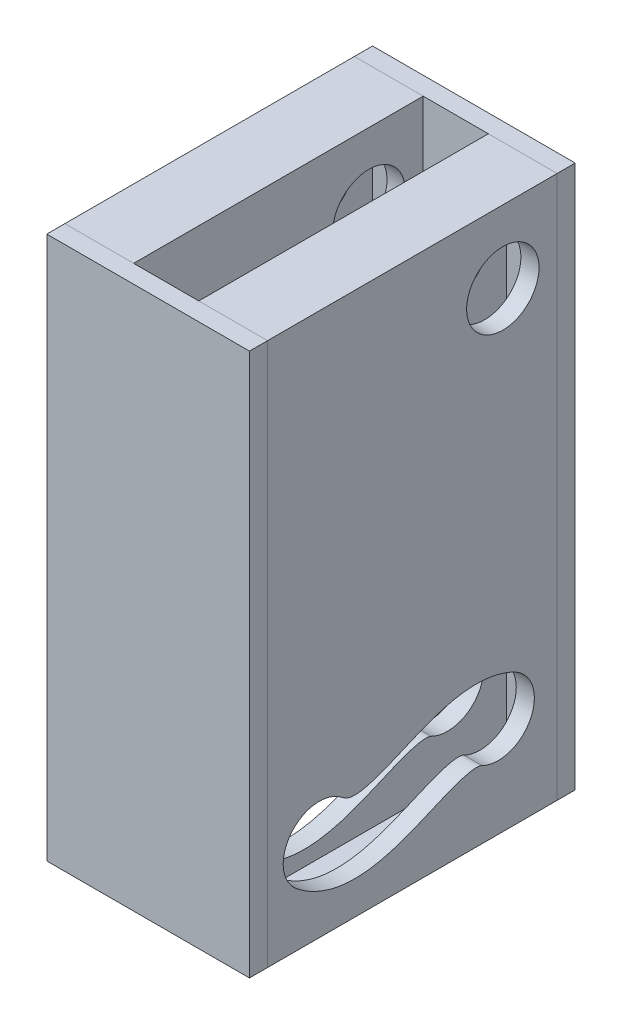
SolidWorks part; units mm, degrees
ref_plane "Front Plane" through (0, 0, 0) normal (0, 0, 1) x (1, 0, 0)
ref_plane "Top Plane" through (0, 0, 0) normal (0, 1, 0) x (1, 0, 0)
ref_plane "Right Plane" through (0, 0, 0) normal (1, 0, 0) x (0, 0, -1)
sketch "Sketch1" plane through (0, 0, 0) normal (0, 0, 1) x (1, 0, 0)
  line L0 (-9, 75) -> (-9, 35)
  line L8 (-9, -35) -> (-9, -75)
  line L9 (-9, -75) -> (-28, -75)
  line L10 (-28, -75) -> (-28, 75)
  line L11 (-28, 75) -> (-9, 75)
  line L12 (0, 171.0434) -> (0, -171.0434) construction
  line L13 (-9, 35) -> (9, 35)
  line L14 (-9, -35) -> (9, -35)
  line L15 (9, -35) -> (9, -75)
  line L16 (9, -75) -> (28, -75)
  line L17 (28, -75) -> (28, 75)
  line L18 (9, 75) -> (9, 35)
  line L19 (28, 75) -> (9, 75)
  line L20 (-23, 70) -> (-14, 70)
  line L21 (-14, 70) -> (-14, 30)
  line L22 (-14, 30) -> (14, 30)
  line L23 (14, 70) -> (14, 30)
  line L24 (23, 70) -> (14, 70)
  line L25 (23, -70) -> (23, 70)
  line L26 (14, -70) -> (23, -70)
  line L27 (14, -30) -> (14, -70)
  line L28 (-14, -30) -> (14, -30)
  line L29 (-14, -30) -> (-14, -70)
  line L30 (-14, -70) -> (-23, -70)
  line L31 (-23, -70) -> (-23, 70)
  line L32 (-66.2515, 55) -> (66.2515, 55) construction
  line L33 (-23, 0) -> (23, 0) construction
  line L34 (-28, 65) -> (28, 65) construction
  line L35 (-28, -65) -> (28, -65) construction
  line L36 (-66.2515, -55) -> (66.2515, -55) construction
  point P6 (0, -35)
  point P16 (0, 35)
  point P31 (0, 0)
  point P34 (0, 55)
  point P35 (-9, 55)
  dimension "D2" = 10
  dimension "D3" = 18
  dimension "D4" = 56
  dimension "D5" = 150
  dimension "D6" = 20
  dimension "D1" = 5
sketch "Sketch2" plane through (0, 0, 0) normal (1, 0, 0) x (0, 0, -1)
  line L0 (-30, 0) -> (50, 0) construction
  line L1 (-30, 0) -> (-35, 0) construction
  line L2 (50, 0) -> (55, 0) construction
  dimension "D1" = 80
  dimension "D2" = 5
  dimension "D3" = 50
extrude "Boss-Extrude1" add sketch "Sketch1" along normal up to vertex (30 mm away) and the other way up to vertex (50 mm away) up to point (0, 0, 30) other way up to point (0, 0, -50)
sketch "Sketch3" plane through (0, 0, 0) normal (0, 0, 1) x (1, 0, 0)
  line L1 (-28, -75) -> (28, -75)
  line L2 (-28, -75) -> (-28, 75)
  line L3 (-28, 75) -> (28, 75)
  line L4 (28, -75) -> (28, 75)
  line L5 (-28, -75) -> (28, 75) construction
  line L6 (-28, 75) -> (28, -75) construction
  point P0 (0, 0)
extrude "Boss-Extrude2" add sketch "Sketch3" along normal up to vertex (35 mm away) from vertex separate body up to point (0, 0, 35) starting at point (0, 0, 30)
extrude "Boss-Extrude3" add sketch "Sketch3<2>" against normal up to vertex (55 mm away) from vertex separate body up to point (0, 0, -55) starting at point (0, 0, -50)
sketch "Sketch3<2>" plane through (0, 0, 0) normal (0, 0, 1) x (1, 0, 0) same geometry as "Sketch3"
sketch "Sketch4" plane through (0, 0, 0) normal (1, 0, 0) x (0, 0, -1)
  line L0 (0, 171.0434) -> (0, -171.0434) construction
  line L1 (0, 0) -> (0, 55) construction
  line L2 (0, 55) -> (35, 55) construction
  line L3 (-11.8844, -55.7997) -> (0.1156, -55.7997) construction
  line L5 (-10.8844, -60.7997) -> (-0.8844, -60.7997) construction
  line L6 (-10.8844, -60.7997) -> (-10.8844, -50.7997) construction
  line L7 (-10.8844, -50.7997) -> (-0.8844, -50.7997) construction
  line L8 (-0.8844, -60.7997) -> (-0.8844, -50.7997) construction
  line L9 (-10.8844, -60.7997) -> (-0.8844, -50.7997) construction
  line L10 (-10.8844, -50.7997) -> (-0.8844, -60.7997) construction
  arc A2 (-21.9612, -60.1535) -> (-9.4142, -44.5787) centre (-15.6877, -52.3661) cw
  arc A3 (29.2096, -56.2677) -> (38.2188, -38.4118) centre (33.7142, -47.3397) ccw
  circle A4 centre (35, 55) radius 10
  spline S0 degree 3 poles (-15.6877, -52.3661) (-0.6676, -64.4663) (19.4244, -40.1299) (33.7142, -47.3397) knots 0 0 0 0 1 1 1 1 construction
  spline S1 degree 1 poles (-21.9612, -60.1535) (29.2096, -56.2677) knots 0 0 1 1 construction
  spline S2 degree 3 poles (-21.9612, -60.1535) (-21.2326, -60.7404) (-19.7049, -61.8467) (-16.5047, -63.6733) (-12.2723, -65.2199) (-7.2245, -65.9156) (-0.896, -65.6402) (6.0756, -63.823) (13.3281, -60.8744) (19.6872, -58.0691) (24.0439, -56.5285) (26.6043, -56.0154) (27.9543, -55.9488) (28.7219, -56.0631) (29.04, -56.1821) (29.2096, -56.2677) knots 0 0 0 0 0.03125 0.0625 0.125 0.1875 0.25 0.375 0.5 0.625 0.75 0.8125 0.875 0.9375 1 1 1 1
  spline S3 degree 1 poles (-9.4142, -44.5787) (38.2188, -38.4118) knots 0 0 1 1 construction
  spline S4 degree 3 poles (-9.4142, -44.5787) (-9.3177, -44.6565) (-9.113, -44.8128) (-8.7501, -45.0598) (-8.3333, -45.2957) (-7.8736, -45.4934) (-7.2533, -45.6849) (-6.3508, -45.8249) (-4.8225, -45.7841) (-2.8135, -45.4329) (0.4161, -44.5109) (5.2569, -42.5771) (11.8945, -39.6457) (18.0981, -37.3535) (23.6968, -36.1642) (28.2903, -35.8349) (32.4283, -36.3113) (35.7677, -37.2971) (37.4231, -38.0103) (38.2188, -38.4118) knots 0 0 0 0 0.015625 0.03125 0.0625 0.09375 0.125 0.1875 0.25 0.3125 0.375 0.5 0.625 0.75 0.8125 0.875 0.9375 0.96875 1 1 1 1
  point P10 (0, -55)
  point P31 (-5.8844, -55.7997)
  dimension "D1" = 10
  dimension "D2" = 10
  dimension "D4" = 35
  dimension "D5" = 20
  dimension "D6" = 12
  dimension "D3" = 10
extrude "Cut-Extrude1" cut sketch "Sketch4" against normal through all and the other way through all contours A4 | S4 A2 S2 A3 L8 L5 L6 L7 | L5 L8 L7 L6 region at (0, -50.8563, -8.874) region at (0, 55, -35)
